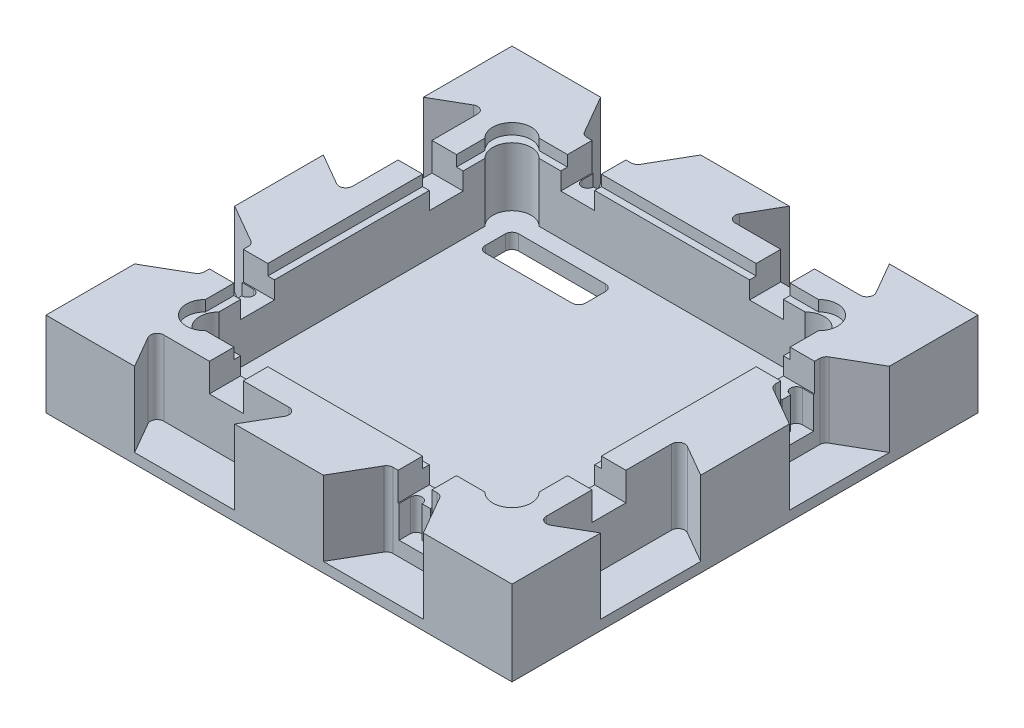
SolidWorks part; units mm, degrees
material "Macor"
ref_plane "Front Plane" through (0, 0, 0) normal (0, 0, 1) x (1, 0, 0)
ref_plane "Top Plane" through (0, 0, 0) normal (0, 1, 0) x (1, 0, 0)
ref_plane "Right Plane" through (0, 0, 0) normal (1, 0, 0) x (0, 0, -1)
sketch "Sketch1" plane through (0, 0, 0) normal (0, 1, 0) x (1, 0, 0)
  line L1 (-69.85, -69.85) -> (69.85, -69.85)
  line L2 (-69.85, -69.85) -> (-69.85, 69.85)
  line L3 (-69.85, 69.85) -> (69.85, 69.85)
  line L4 (69.85, -69.85) -> (69.85, 69.85)
  line L5 (-69.85, -69.85) -> (69.85, 69.85) construction
  line L6 (-69.85, 69.85) -> (69.85, -69.85) construction
  point P0 (0, 0)
  dimension "D1" = 139.7
extrude "Boss-Extrude1" add sketch "Sketch1" along normal mid plane 25.4
sketch "Sketch6" plane through (0, 12.7, 0) normal (0, 1, 0) x (1, 0, 0)
  line L0 (-48, 39.8683) -> (-48, -39.8683)
  line L1 (-48, -48) -> (48, -48) construction
  line L2 (-48, -48) -> (-48, 48) construction
  line L3 (-48, 48) -> (48, 48) construction
  line L4 (48, -48) -> (48, 48) construction
  line L5 (-48, -48) -> (48, 48) construction
  line L6 (-48, 48) -> (48, -48) construction
  line L7 (-39.8683, -48) -> (39.8683, -48)
  line L8 (39.8683, 48) -> (-39.8683, 48)
  line L9 (48, 39.8683) -> (48, -39.8683)
  arc A0 (-39.8683, 48) -> (-48, 39.8683) centre (-43.9341, 43.9341) ccw
  arc A1 (48, 39.8683) -> (39.8683, 48) centre (43.9341, 43.9341) ccw
  arc A2 (39.8683, -48) -> (48, -39.8683) centre (43.9341, -43.9341) ccw
  arc A3 (-48, -39.8683) -> (-39.8683, -48) centre (-43.9341, -43.9341) ccw
  point P0 (0, 0)
  point P21 (0, 0)
  dimension "D2" = 5.75
  dimension "D1" = 96
  dimension "D3" = 4
extrude "power_supply_component_depth" cut sketch "Sketch6" against normal offset from surface (20.9 mm away) 4.5 up to face at (0, -12.7, 0)
ref_axis "Axis1" through (0, -25.4398, 0) along (0, 1, 0)
sketch "Sketch4" plane through (0, 12.7, 0) normal (0, 1, 0) x (1, 0, 0)
  line L0 (-43.2833, -69.85) -> (-50.5002, -57.35)
  line L1 (-69.85, -69.85) -> (69.85, -69.85) construction
  line L2 (-50.5002, -57.35) -> (-6.0665, -57.35)
  line L3 (-6.0665, -57.35) -> (-13.2833, -69.85)
  line L4 (-13.2833, -69.85) -> (-43.2833, -69.85)
  line L5 (43.2833, -69.85) -> (36.0665, -57.35)
  line L24 (43.2833, -69.85) -> (13.2833, -69.85)
  line L25 (-69.85, -69.85) -> (-43.2833, -69.85) construction
  line L26 (-13.2833, -69.85) -> (13.2833, -69.85) construction
  line L27 (43.2833, -69.85) -> (69.85, -69.85) construction
  line L28 (36.0665, -57.35) -> (20.5002, -57.35)
  line L30 (13.2833, -69.85) -> (20.5002, -57.35)
  dimension "D2" = 30
  dimension "D1" = 60
  dimension "D3" = 12.5
  dimension "D4" = 60
  dimension "D5" = 26.5667
extrude "Cut-Extrude6" cut sketch "Sketch4" against normal offset from surface (22.4 mm away) 3 up to face at (0, -12.7, 0)
sketch "Sketch8" plane through (0, 12.7, 0) normal (0, 1, 0) x (1, 0, 0)
  line L0 (-28.2833, -57.35) -> (-28.2833, -52.675) construction
  line L1 (-6.0665, -57.35) -> (-50.5002, -57.35) construction
  line L2 (28.2833, -57.35) -> (28.2833, -52.675) construction
  line L3 (36.0665, -57.35) -> (20.5002, -57.35) construction
  line L5 (-33.3633, -57.35) -> (-23.2033, -57.35)
  line L6 (-33.3633, -57.35) -> (-33.3633, -48)
  line L7 (-33.3633, -48) -> (-23.2033, -48)
  line L8 (-23.2033, -57.35) -> (-23.2033, -48)
  line L9 (-33.3633, -57.35) -> (-23.2033, -48) construction
  line L10 (-33.3633, -48) -> (-23.2033, -57.35) construction
  line L11 (36.0665, -57.35) -> (20.5002, -57.35) construction
  line L12 (23.2033, -57.35) -> (33.3633, -57.35)
  line L13 (23.2033, -57.35) -> (23.2033, -48)
  line L14 (23.2033, -48) -> (33.3633, -48)
  line L15 (33.3633, -57.35) -> (33.3633, -48)
  line L16 (23.2033, -57.35) -> (33.3633, -48) construction
  line L17 (23.2033, -48) -> (33.3633, -57.35) construction
  line L18 (-39.8683, -48) -> (39.8683, -48) construction
  dimension "D1" = 10.16
extrude "Cut-Extrude7" cut sketch "Sketch8" against normal blind 8.48
sketch "Sketch9" plane through (0, 4.22, 0) normal (0, 1, 0) x (1, 0, 0)
  line L0 (28.2833, -57.35) -> (28.2833, -55.6625) construction
  line L1 (36.0665, -57.35) -> (20.5002, -57.35) construction
  line L2 (27.0183, -53.975) -> (29.5483, -53.975)
  line L3 (23.5183, -53.975) -> (33.0483, -53.975) construction
  line L4 (23.5183, -53.975) -> (23.5183, -57.35)
  line L5 (23.5183, -57.35) -> (33.0483, -57.35)
  line L6 (33.0483, -53.975) -> (33.0483, -57.35)
  line L7 (23.5183, -53.975) -> (33.0483, -57.35) construction
  line L8 (23.5183, -57.35) -> (33.0483, -53.975) construction
  arc A0 (23.5183, -53.975) -> (27.0183, -53.975) centre (25.2683, -53.975) cw
  arc A1 (33.0483, -53.975) -> (29.5483, -53.975) centre (31.2983, -53.975) ccw
  dimension "D3" = 1.75
  dimension "D1" = 9.53
  dimension "D2" = 3.375
extrude "Cut-Extrude8" cut sketch "Sketch9" against normal blind 9.53
fillet "Fillet2" radius 2 4 edges at (20.5002, 1.5, 57.35) (36.0665, 1.5, 57.35) (-6.0665, 1.5, 57.35) (-50.5002, 1.5, 57.35)
pattern_circular "CirPattern5" count 4 over 360 about axis through (0, -25.4398, 0) along (0, 1, 0) of "Cut-Extrude6", "Cut-Extrude7", "Cut-Extrude8", "Fillet2"
sketch "Sketch10" plane through (0, 12.7, 0) normal (0, 1, 0) x (1, 0, 0)
  line L0 (-41.8683, 50) -> (41.8683, 50)
  line L1 (-50, -50) -> (50, -50) construction
  line L2 (-50, -50) -> (-50, 50) construction
  line L3 (-50, 50) -> (50, 50) construction
  line L4 (50, -50) -> (50, 50) construction
  line L5 (-50, -50) -> (50, 50) construction
  line L6 (-50, 50) -> (50, -50) construction
  line L7 (50, 41.8683) -> (50, -41.8683)
  line L8 (41.8683, -50) -> (-41.8683, -50)
  line L9 (-50, -41.8683) -> (-50, 41.8683)
  arc A0 (41.8683, 50) -> (50, 41.8683) centre (45.9341, 45.9341) cw
  arc A1 (50, -41.8683) -> (41.8683, -50) centre (45.9341, -45.9341) cw
  arc A2 (-41.8683, -50) -> (-50, -41.8683) centre (-45.9341, -45.9341) cw
  arc A3 (-50, 41.8683) -> (-41.8683, 50) centre (-45.9341, 45.9341) cw
  point P0 (0, 0)
  point P21 (0, 0)
  dimension "D2" = 5.75
  dimension "D1" = 100
  dimension "D3" = 4
extrude "Cut-Extrude9" cut sketch "Sketch10" against normal blind 3.25
sketch "Sketch12" plane through (0, -8.2, 0) normal (0, 1, 0) x (1, 0, 0)
  line L0 (39.8683, 48) -> (-39.8683, 48) construction
  line L1 (-43, 43) -> (-13, 43)
  line L2 (-43, 43) -> (-43, 33)
  line L3 (-43, 33) -> (-13, 33)
  line L4 (-13, 43) -> (-13, 33)
  line L5 (-48, 23.2033) -> (-48, 33.3633) construction
  dimension "D1" = 5
  dimension "D2" = 5
  dimension "D3" = 30
  dimension "D4" = 10
extrude "Cut-Extrude10" cut sketch "Sketch12" against normal through all and the other way through all
fillet "Fillet5" radius 2 4 edges at (-43, -10.45, -43) (-13, -10.45, -43) (-13, -10.45, -33) (-43, -10.45, -33)
pattern_circular "CirPattern6" count 2 over 360 about axis through (0, -25.4398, 0) along (0, 1, 0) of "Fillet5", "Cut-Extrude10"
sketch "sussy_baka_uwu" plane through (0, -8.2, 0) normal (0, 1, 0) x (1, 0, 0)
  line L0 (-13, 41) -> (-13, 35) construction
  line L1 (-15, 33) -> (-41, 33) construction
  line L2 (-43, 35) -> (-43, 41) construction
  line L3 (-41, 43) -> (-15, 43) construction
  line L4 (-13, 41) -> (-13, 35)
  line L5 (-15, 33) -> (-41, 33)
  line L6 (-43, 35) -> (-43, 41)
  line L7 (-41, 43) -> (-15, 43)
  line L8 (9.2262, 43) -> (9.2262, -5.178)
  line L9 (-35.7752, 33) -> (-35.7752, -5.178)
  line L10 (-35.7752, -5.178) -> (-25.7958, -5.178)
  line L11 (-25.7958, -5.178) -> (-25.7958, 3.1068)
  line L12 (-25.7958, 3.1068) -> (-3.3892, 3.1068)
  line L13 (-3.3892, 3.1068) -> (-3.3892, -5.178)
  line L14 (-3.3892, -5.178) -> (9.2262, -5.178)
  line L15 (9.2262, 39.0703) -> (19.3939, 39.0703)
  line L16 (19.3939, 39.0703) -> (19.3939, 12.333)
  line L17 (19.3939, 12.333) -> (9.2262, 12.333)
  arc A0 (-13, 41) -> (-15, 43) centre (-15, 41) ccw construction
  arc A1 (-15, 33) -> (-13, 35) centre (-15, 35) ccw construction
  arc A2 (-43, 35) -> (-41, 33) centre (-41, 35) ccw construction
  arc A3 (-41, 43) -> (-43, 41) centre (-41, 41) ccw construction
  arc A4 (-13, 41) -> (-15, 43) centre (-15, 41) ccw
  arc A5 (-15, 33) -> (-13, 35) centre (-15, 35) ccw
  arc A6 (-43, 35) -> (-41, 33) centre (-41, 35) ccw
  arc A7 (-41, 43) -> (-43, 41) centre (-41, 41) ccw
  arc A8 (-35.7752, 43) -> (9.2262, 43) centre (-13.2745, 42.7666) cw
equation "\"panel_width\"= 5.5in"
equation "\"finger_joint_width\"= 30mm"
equation "\"D1@Sketch1\"=\"panel_width\""
equation "\"D2@Sketch4\"=\"finger_joint_width\""
